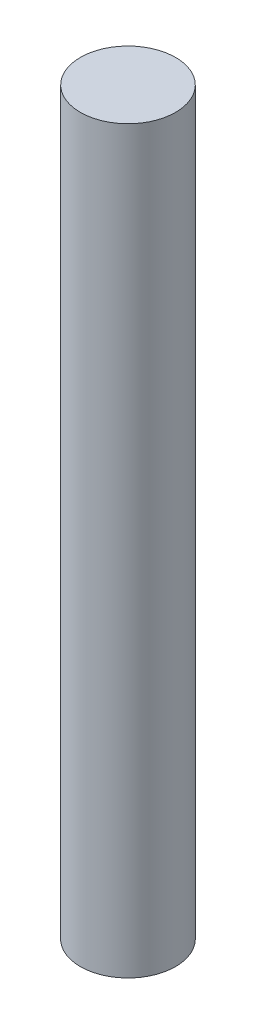
SolidWorks part; units mm, degrees
ref_plane "Front Plane" through (0, 0, 0) normal (0, 0, 1) x (1, 0, 0)
ref_plane "Top Plane" through (0, 0, 0) normal (0, 1, 0) x (1, 0, 0)
ref_plane "Right Plane" through (0, 0, 0) normal (1, 0, 0) x (0, 0, -1)
sketch "Sketch1" plane through (0, 0, 0) normal (0, 1, 0) x (1, 0, 0)
  circle A0 centre (0, 0) radius 3.175
  dimension "D1" = 6.35
sketch "Sketch2" plane through (0, 0, 0) normal (1, 0, 0) x (0, 0, -1)
  line L0 (0, 0) -> (0, 49.3255)
  circle A0 centre (0, 0) radius 49.3255 construction
extrude "Boss-Extrude1" add sketch "Sketch1" along normal up to vertex (49.3255 mm away) contours A0 up to point (0, 49.3255, 0)
